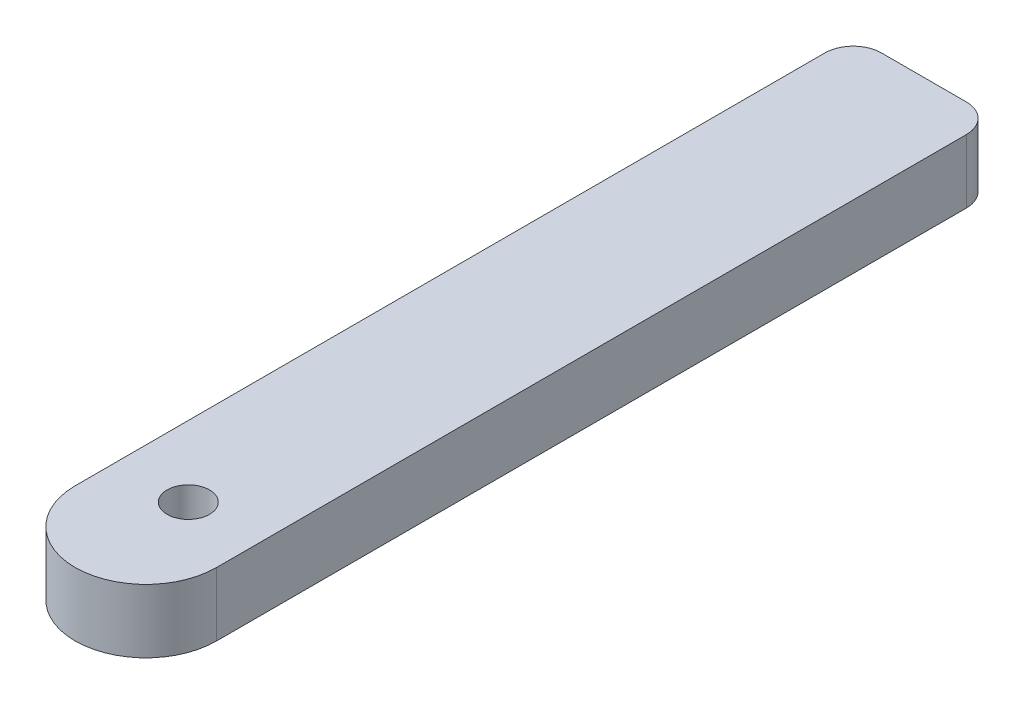
SolidWorks part; units mm, degrees
ref_plane "Plan de face" through (0, 0, 0) normal (0, 0, 1) x (1, 0, 0)
ref_plane "Plan de dessus" through (0, 0, 0) normal (0, 1, 0) x (1, 0, 0)
ref_plane "Plan de droite" through (0, 0, 0) normal (1, 0, 0) x (0, 0, -1)
sketch "Esquisse1" plane through (0, 0, 0) normal (0, 1, 0) x (1, 0, 0)
  line L0 (0, 0) -> (0, 40) construction
  line L1 (5, 40) -> (-5, 40)
  line L2 (-5, 40) -> (-5, -15)
  line L3 (5, 40) -> (5, -15)
  arc A0 (-5, -15) -> (5, -15) centre (0, -15) ccw
  circle A1 centre (0, -12) radius 1.5
  point P0 (0, 0)
  point P13 (-5, 40)
  dimension "D2" = 5
  dimension "D5" = 3
  dimension "D6" = 12
  dimension "D7" = 5
  dimension "D1" = 5
  dimension "D3" = 40
  dimension "D4" = 15
extrude "Boss.-Extru.1" add sketch "Esquisse1" along normal blind 4.5
fillet "Congé1" radius 2 2 edges at (-5, 2.25, -40) (5, 2.25, -40)
